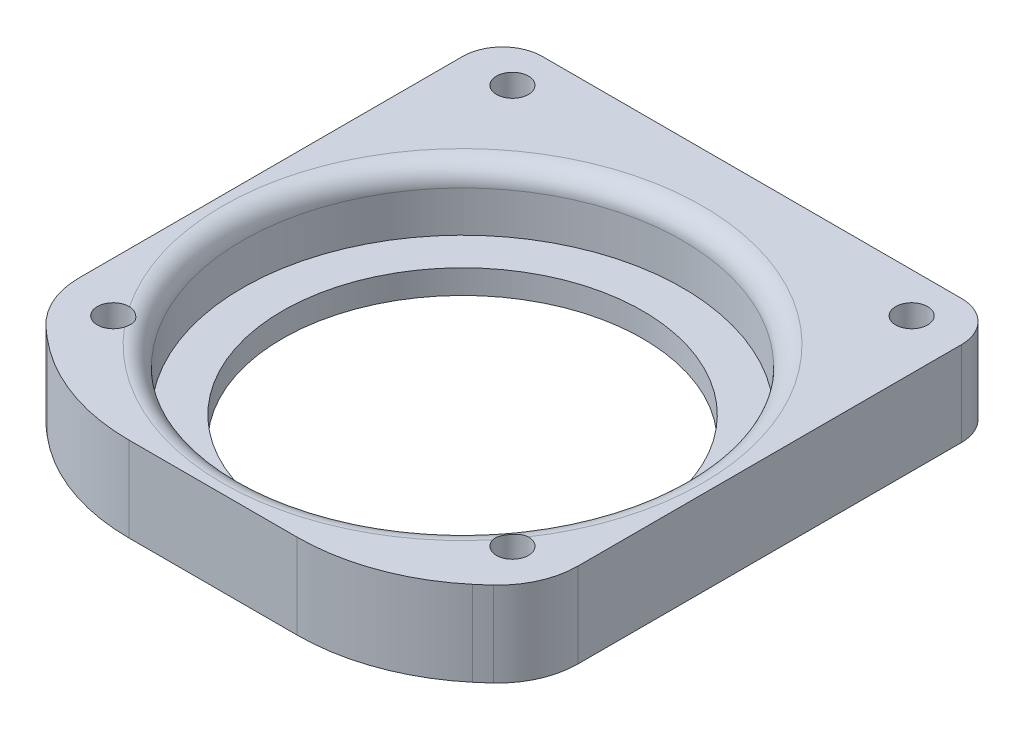
SolidWorks part; units mm, degrees
ref_plane "前视基准面" through (0, 0, 0) normal (0, 0, 1) x (1, 0, 0)
ref_plane "上视基准面" through (0, 0, 0) normal (0, 1, 0) x (1, 0, 0)
ref_plane "右视基准面" through (0, 0, 0) normal (1, 0, 0) x (0, 0, -1)
sketch "草图1" plane through (0, 0, 0) normal (0, 1, 0) x (1, 0, 0)
  circle A0 centre (0, 0) radius 25
extrude "凸台-拉伸1" add sketch "草图1" along normal blind 8.5
sketch "草图2" plane through (0, 8.5, 0) normal (0, 1, 0) x (1, 0, 0)
  circle A0 centre (0, 0) radius 22.05
  dimension "D1" = 44.1
extrude "切除-拉伸1" cut sketch "草图2" against normal blind 6.1
sketch "草图3" plane through (0, 2.4, 0) normal (0, 1, 0) x (1, 0, 0)
  circle A0 centre (0, 0) radius 18.05
  circle A1 centre (0, 0) radius 22.05 construction
  dimension "D1" = 4
extrude "切除-拉伸2" cut sketch "草图3" against normal blind 12.5
sketch "草图4" plane through (0, 0, 0) normal (0, 1, 0) x (1, 0, 0)
  line L1 (-25, 25) -> (25, 25)
  line L2 (-25, 25) -> (-25, -25)
  line L3 (-25, -25) -> (25, -25)
  line L4 (25, 25) -> (25, -25)
  line L5 (-25, 25) -> (25, -25) construction
  line L6 (-25, -25) -> (25, 25) construction
  circle A0 centre (0, 0) radius 25
  point P0 (0, 0)
  point P20 (0.1152, -0.1152)
  dimension "D1" = 50
  dimension "D2" = 50
fillet "圆角2" radius 2 1 edges at (0, 8.5, 22.05)
sketch "草图6" plane through (0, 0, 0) normal (0, -1, 0) x (1, 0, 0)
  line L0 (0, 25) -> (0, -25) construction
  line L2 (-20, 15) -> (20, 15) construction
  line L3 (-20, 15) -> (-20, -25) construction
  line L4 (-20, -25) -> (20, -25) construction
  line L5 (20, 15) -> (20, -25) construction
  line L6 (-20, 15) -> (20, -25) construction
  line L7 (-20, -25) -> (20, 15) construction
  circle A0 centre (0, 0) radius 25 construction
  point P5 (0, -5)
  dimension "D1" = 40
  dimension "D2" = 40
  dimension "D3" = 5
sketch "草图7" plane through (0, 0, 0) normal (0, -1, 0) x (1, 0, 0)
  line L0 (-20, 15) -> (-20, -25) construction
  line L1 (0, 25) -> (25, 25)
  line L2 (0, 25) -> (0, -29)
  line L3 (0, -29) -> (25, -29)
  line L4 (25, 25) -> (25, -29)
  line L5 (0, 25) -> (-25, 25)
  line L6 (0, 25) -> (0, -29)
  line L7 (0, -29) -> (-25, -29)
  line L8 (-25, 25) -> (-25, -29)
  line L9 (20, 15) -> (20, -25) construction
  line L10 (-20, -25) -> (20, -25) construction
  circle A0 centre (0, 0) radius 25
  circle M5 centre (0, 0) radius 25
  dimension "D1" = 5
  dimension "D2" = 5
  dimension "D3" = 4
extrude "凸台-拉伸3" add sketch "草图7" against normal blind 8.5 contours L5 L8 M5 | L4 L1 M5 | L4 L2 L3 M5 | L8 L7 L2 M5 region at (-19.4158, 0, 19.4158) region at (19.4158, 0, 19.4158) region at (16.4619, 0, -22.6552) region at (-16.4619, 0, -22.6552)
sketch "草图8" plane through (0, 0, 0) normal (0, -1, 0) x (1, 0, 0)
  circle A0 centre (-20, 15) radius 1.6
  circle A1 centre (-20, 15) radius 3.2
  circle A2 centre (20, 15) radius 3.2
  circle A3 centre (20, 15) radius 1.6
  circle A4 centre (20, -25) radius 3.2
  circle A5 centre (20, -25) radius 1.6
  circle A6 centre (-20, -25) radius 3.2
  circle A7 centre (-20, -25) radius 1.6
  point P16 (0, -5)
  dimension "D1" = 6.4
  dimension "D2" = 3.2
  dimension "D3" = 4
extrude "切除-拉伸3" cut sketch "草图8" against normal blind 2
extrude "切除-拉伸4" cut sketch "草图8<2>" against normal blind 10 contours A0 | A3 | A7 | A5
sketch "草图8<2>" plane through (0, 0, 0) normal (0, -1, 0) x (1, 0, 0) same geometry as "草图8"
fillet "圆角3" radius 4 2 edges at (25, 4.25, -29) (-25, 4.25, -29)
sketch "草图9" plane through (0, 0, 0) normal (0, -1, 0) x (1, 0, 0)
  line L0 (-25, 16.6567) -> (-25, 25)
  line L1 (-25, 25) -> (-25, -25) construction
  line L2 (-25, 25) -> (25, 25)
  line L3 (25, 25) -> (25, 16.6567)
  line L4 (25, 25) -> (25, -25) construction
  arc A0 (-13.9288, 25) -> (-25, 16.6567) centre (0, -5) ccw
  arc A1 (25, 16.6567) -> (13.9288, 25) centre (0, -5) ccw
  line M8 (25, -25) -> (25, 25)
  line M9 (25, 25) -> (-25, 25)
  line M10 (-25, 25) -> (-25, -25)
extrude "切除-拉伸5" cut sketch "草图9" against normal blind 10 contours A0 L2 M10 | A1 M8 M9 region at (21.5978, 0, 22.4185) region at (-21.5978, 0, 22.4185)
fillet "圆角5" radius 8 2 edges at (25, 4.25, 16.6567) (-25, 4.25, 16.6567)
fillet "圆角6" radius 20 2 edges at (13.9288, 4.25, 25) (-13.9288, 4.25, 25)
